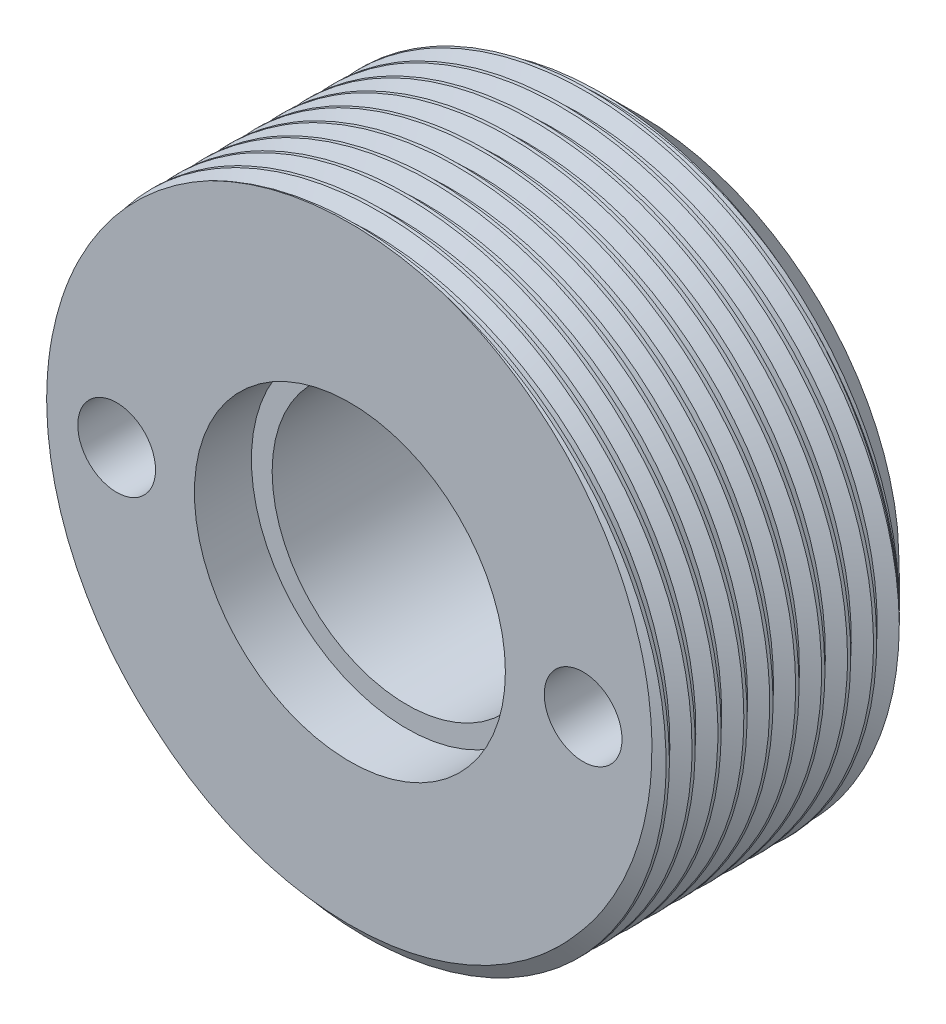
SolidWorks part; units mm, degrees
ref_plane "Спереди" through (0, 0, 0) normal (0, 0, 1) x (1, 0, 0)
ref_plane "Сверху" through (0, 0, 0) normal (0, 1, 0) x (1, 0, 0)
ref_plane "Справа" through (0, 0, 0) normal (1, 0, 0) x (0, 0, -1)
sketch "Эскиз1" plane through (0, 0, 0) normal (0, 0, 1) x (1, 0, 0)
  circle A0 centre (0, 0) radius 6
  dimension "D1" = 12
extrude "Бобышка-Вытянуть1" add sketch "Эскиз1" along normal blind 5.6
chamfer "Фаска3" distance 1 angle 45 1 edges at (6, 0, 0)
sketch "Эскиз2" plane through (0, 0, 5.6) normal (0, 0, 1) x (1, 0, 0)
  circle A0 centre (0, 0) radius 3
  dimension "D1" = 6
extrude "Вырез-Вытянуть1" cut sketch "Эскиз2" against normal blind 1.1
sketch "Эскиз3" plane through (0, 0, 4.5) normal (0, 0, 1) x (1, 0, 0)
  circle A0 centre (0, 0) radius 2.6
  dimension "D1" = 5.2
extrude "Вырез-Вытянуть2" cut sketch "Эскиз3" against normal blind 4.5
sketch "Эскиз4" plane through (0, 0, 5.6) normal (0, 0, 1) x (1, 0, 0)
  line L5 (-3, 0) -> (-6, 0) construction
  line L6 (0, 6) -> (0, -6) construction
  circle A0 centre (-4.5, 0) radius 0.75
  circle A1 centre (0, 0) radius 3 construction
  circle A2 centre (0, 0) radius 3 construction
  circle A3 centre (0, 0) radius 6 construction
  circle A4 centre (4.5, 0) radius 0.75
  dimension "D1" = 1.5
extrude "Вырез-Вытянуть3" cut sketch "Эскиз4" against normal through all and the other way blind 0.5
thread "Резьба1" pitch 0.5 method cut profile "Профиль резьбы1" start angle 0, offset 2, length 10, pitch 0.5, diameter 12
ref_plane "Плоскость1" through (6, 0, -1) normal (0, -1, 0) x (1, 0, 0)
sketch "Профиль резьбы1" plane through (6, 0, -1) normal (0, -1, 0) x (1, 0, 0)
  line L0 (0, 0) -> (0, 0.5) construction
  line L11 (0, 0) -> (0, 0.4375)
  line L12 (0, 0.4375) -> (-0.2706, 0.2812)
  line L13 (-0.2706, 0.2812) -> (-0.2706, 0.1562)
  line L15 (-0.2706, 0.1562) -> (0, 0)
  line L17 (-0.2706, 0.2187) -> (0, 0.2187) construction
  point P2 (0, 0)
  dimension "Pitch" = 0.5
  dimension "Profile_Angle" = 60
  dimension "Profile_Land" = 0.125
  dimension "Profile_Height" = 0.2706
